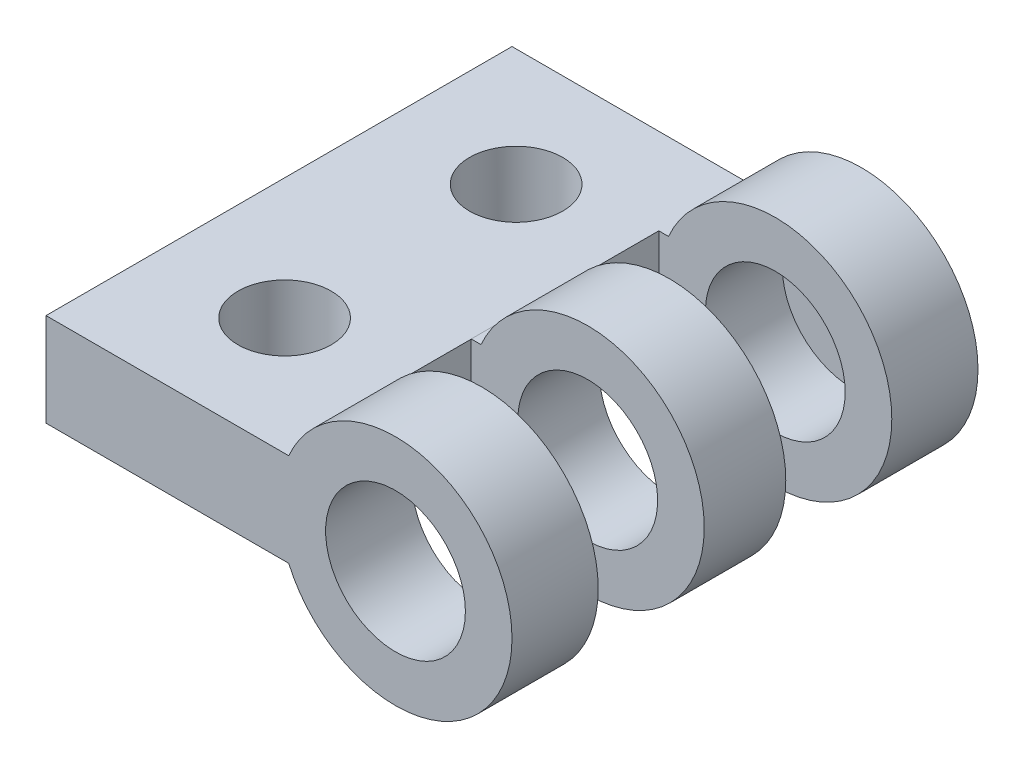
SolidWorks part; units mm, degrees
ref_plane "Front Plane" through (0, 0, 0) normal (0, 0, 1) x (1, 0, 0)
ref_plane "Top Plane" through (0, 0, 0) normal (0, 1, 0) x (1, 0, 0)
ref_plane "Right Plane" through (0, 0, 0) normal (1, 0, 0) x (0, 0, -1)
sketch "Sketch1" plane through (0, 0, 0) normal (0, 0, 1) x (1, 0, 0)
  circle A0 centre (0, 0) radius 2.5
  circle A1 centre (0, 0) radius 1.5
  dimension "D1" = 5
  dimension "D2" = 3
extrude "Boss-Extrude2" add sketch "Sketch1" along normal blind 1.95
sketch "Sketch6" plane through (0, 0, 0) normal (1, 0, 0) x (0, 0, -1)
  line L0 (0.3584, 2.6698) -> (0.3584, -2.6698) construction
  point P3 (0.3584, 0)
sketch "Sketch7" plane through (0, 0, 0) normal (0, 1, 0) x (1, 0, 0)
  line L0 (1.5, 0) -> (-1.5, 0) construction
  line L1 (-7.5, 0) -> (-2.5, 0)
  line L2 (-7.5, 0) -> (-7.5, -10)
  line L3 (-7.5, -10) -> (-2.5, -10)
  line L4 (-2.5, 0) -> (-2.5, -10)
  line L5 (-2.5, 0) -> (-2.5, -1.95) construction
  dimension "D1" = 10
  dimension "D2" = 0
  dimension "D3" = 0
  dimension "D4" = 5
extrude "Boss-Extrude3" add sketch "Sketch7" along normal blind 1 and the other way blind 1 separate body
sketch "Sketch8" plane through (-2.5, 0, 0) normal (1, 0, 0) x (0, 0, -1)
  line L0 (-1.95, -1) -> (-1.95, 1)
  line L1 (-1.95, 2.5) -> (-1.95, -2.5) construction
  line L2 (-10, -1) -> (0, -1) construction
  line L3 (-10, 1) -> (0, 1) construction
  line L4 (-1.95, 1) -> (0, 1)
  line L5 (0, 1) -> (0, -1)
  line L6 (0, -1) -> (-1.95, -1)
extrude "Boss-Extrude4" add sketch "Sketch8" along normal up to surface (0.2087 mm away) up to face at (2.5, 0, 0)
sketch "Sketch9" plane through (-2.5, 0, 0) normal (1, 0, 0) x (0, 0, -1)
  line L0 (-10, 0) -> (0, 0) construction
  line L1 (-10, -1) -> (-10, 1) construction
sketch "Sketch10" plane through (0, 0, 10) normal (0, 0, 1) x (1, 0, 0)
  circle A0 centre (0, 0) radius 2.5
  circle A1 centre (0, 0) radius 1.5
extrude "Boss-Extrude5" add sketch "Sketch10" against normal blind 1.95 separate body
sketch "Sketch11" plane through (-2.5, 0, 0) normal (1, 0, 0) x (0, 0, -1)
  line L0 (-5, -3.7452) -> (-5, 3.7452) construction
  point P3 (-5, 0)
ref_plane "Plane1" through (0, 0, 5) normal (0, 0, -1) x (0, 1, 0)
sketch "Sketch12" plane through (0, 0, 5) normal (0, 0, -1) x (0, 1, 0)
  circle A0 centre (0, 0) radius 2.5
  circle A1 centre (0, 0) radius 1.5
extrude "Boss-Extrude6" add sketch "Sketch12" along normal blind 0.975 and the other way blind 0.975 separate body
sketch "Sketch13" plane through (-2.5, 0, 0) normal (1, 0, 0) x (0, 0, -1)
  line L0 (-5.975, 2.5) -> (-5.975, -2.5) construction
  line L1 (-5.975, 1.0029) -> (-4.025, 1.0029)
  line L2 (-5.975, 1.0029) -> (-5.975, -1)
  line L3 (-5.975, -1) -> (-4.025, -1)
  line L4 (-4.025, 1.0029) -> (-4.025, -1)
  line L5 (-10, -1) -> (-1.95, -1) construction
  line L6 (-4.025, -2.5) -> (-4.025, 2.5) construction
  line L7 (-8.05, -2.5) -> (-8.05, 2.5) construction
  line L8 (-8.05, 1) -> (-10, 1)
  line L9 (-8.05, 1) -> (-8.05, -1)
  line L10 (-8.05, -1) -> (-10, -1)
  line L11 (-10, 1) -> (-10, -1)
  line L12 (-10, 1) -> (-1.95, 1) construction
  line L13 (-10, 2.5) -> (-10, -2.5) construction
extrude "Boss-Extrude7" add sketch "Sketch13" along normal up to surface (0.21 mm away) up to face at (2.5, 0, 8.05)
sketch "Sketch14" plane through (0, -1, 0) normal (0, -1, 0) x (-1, 0, 0)
  line L2 (2.5, -8.05) -> (2.5, -5.975) construction
  line L3 (2.5, -4.025) -> (2.5, -1.95) construction
  line L5 (2.5, -7.0125) -> (7.5, -7.0125) construction
  line L7 (7.5, 0) -> (7.5, -10) construction
sketch "Sketch15" plane through (0, 0, 0) normal (0, 0, -1) x (-1, 0, 0)
  circle A0 centre (0, 0) radius 1.5
extrude "Boss-Extrude8" add sketch "Sketch15" against normal blind 0.2
sketch "Sketch16" plane through (0, 1, 0) normal (0, 1, 0) x (1, 0, 0)
  line L0 (-4.8956, -10) -> (-4.8956, -4.9684) construction
  line L3 (-7.5, -10) -> (-2.2913, -10) construction
  line L4 (1.6775, -5) -> (-1.6775, -5) construction
  circle A0 centre (-4.8956, -7.4842) radius 1
  circle A1 centre (-4.8956, -2.5158) radius 1
  dimension "D1" = 2
extrude "Cut-Extrude1" cut sketch "Sketch16" against normal blind 10
sketch "Sketch17" plane through (0, 0, 8.05) normal (0, 0, -1) x (-1, 0, 0)
  line L1 (2.5, 2.74) -> (-2.5, 2.74)
  line L2 (2.5, 2.74) -> (2.5, -2.74)
  line L3 (2.5, -2.74) -> (-2.5, -2.74)
  line L4 (-2.5, 2.74) -> (-2.5, -2.74)
  line L5 (2.5, 2.74) -> (-2.5, -2.74) construction
  line L6 (2.5, -2.74) -> (-2.5, 2.74) construction
  arc A0 (2.2913, 1) -> (2.2913, -1) centre (0, 0) ccw construction
  point P0 (0, 0)
  point P9 (-2.5, 0)
  dimension "D1" = 0
extrude "Cut-Extrude2" cut sketch "Sketch17" against normal blind 0.1
sketch "Sketch18" plane through (0, 0, 5.975) normal (0, 0, 1) x (1, 0, 0)
  line L0 (-2.5, -3.7452) -> (-2.5, 3.7452) construction
  line L1 (2.5, 2.6055) -> (-2.5, 2.6055)
  line L2 (2.5, 2.6055) -> (2.5, -2.6055)
  line L3 (2.5, -2.6055) -> (-2.5, -2.6055)
  line L4 (-2.5, 2.6055) -> (-2.5, -2.6055)
  line L5 (2.5, 2.6055) -> (-2.5, -2.6055) construction
  line L6 (2.5, -2.6055) -> (-2.5, 2.6055) construction
  point P0 (0, 0)
extrude "Cut-Extrude3" cut sketch "Sketch18" against normal blind 0.1
sketch "Sketch19" plane through (0, 0, 4.025) normal (0, 0, -1) x (-1, 0, 0)
  line L1 (2.5, 2.5) -> (-2.5, 2.5)
  line L2 (2.5, 2.5) -> (2.5, -2.5)
  line L3 (2.5, -2.5) -> (-2.5, -2.5)
  line L4 (-2.5, 2.5) -> (-2.5, -2.5)
  line L5 (2.5, 2.5) -> (-2.5, -2.5) construction
  line L6 (2.5, -2.5) -> (-2.5, 2.5) construction
  arc A0 (2.29, 1.0029) -> (2.2913, -1) centre (0, 0) ccw construction
  point P0 (0, 0)
  dimension "D1" = 2.5
  dimension "D2" = 5
extrude "Cut-Extrude5" cut sketch "Sketch19" against normal blind 0.1
sketch "Sketch20" plane through (0, 0, 1.95) normal (0, 0, 1) x (1, 0, 0)
  line L1 (-2.5, 2.7626) -> (2.5, 2.7626)
  line L2 (-2.5, 2.7626) -> (-2.5, -2.7626)
  line L3 (-2.5, -2.7626) -> (2.5, -2.7626)
  line L4 (2.5, 2.7626) -> (2.5, -2.7626)
  line L5 (-2.5, 2.7626) -> (2.5, -2.7626) construction
  line L6 (-2.5, -2.7626) -> (2.5, 2.7626) construction
  arc A0 (-2.2913, -1) -> (-2.2913, 1) centre (0, 0) ccw construction
  point P0 (0, 0)
  point P9 (2.5, 0)
  dimension "D1" = 0
extrude "Cut-Extrude6" cut sketch "Sketch20" against normal blind 0.1
